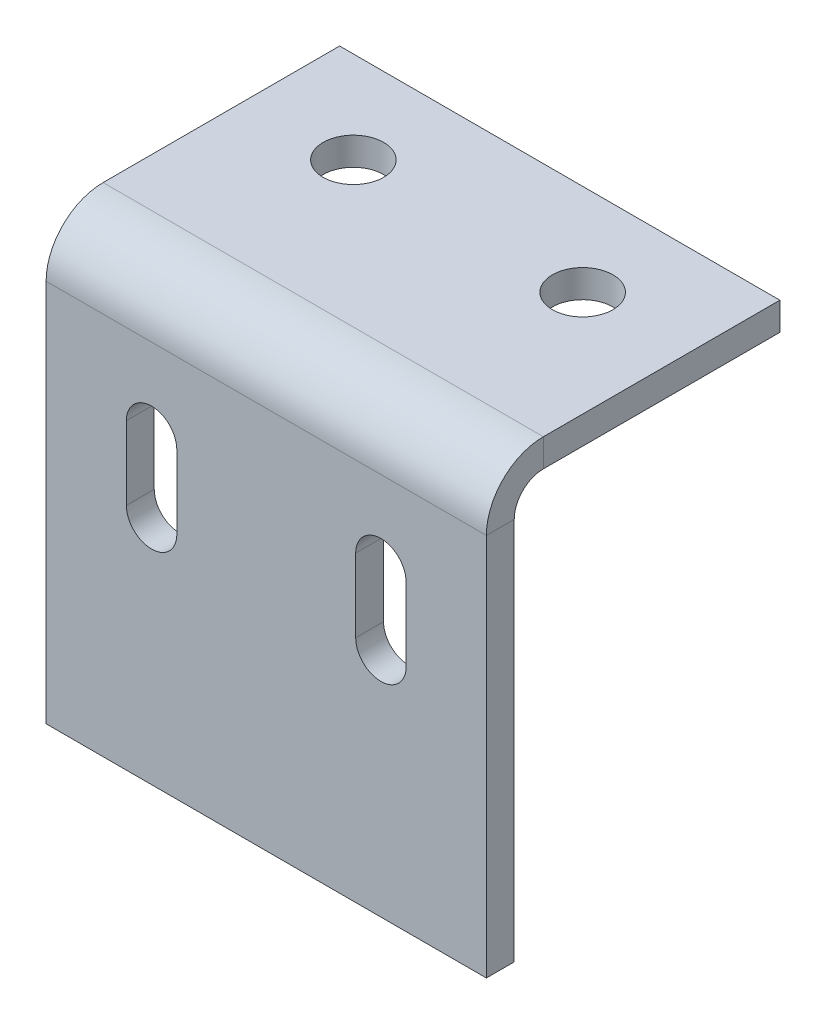
SolidWorks part; units mm, degrees
note: The reader was unsure of these and kept them because the rebuilt part matched: flange length of "Edge-Flange1".
material "Low Carbon Steel"
ref_plane "Front Plane" through (0, 0, 0) normal (0, 0, 1) x (1, 0, 0)
ref_plane "Top Plane" through (0, 0, 0) normal (0, 1, 0) x (1, 0, 0)
ref_plane "Right Plane" through (0, 0, 0) normal (1, 0, 0) x (0, 0, -1)
sketch "Sketch1" plane through (0, 0, 0) normal (0, 1, 0) x (1, 0, 0)
  line L1 (-24, 32) -> (24, 32)
  line L2 (-24, 32) -> (-24, 0)
  line L3 (-24, 0) -> (24, 0)
  line L4 (24, 32) -> (24, 0)
  dimension "D1" = 32
  dimension "D2" = 48
base flange "Base-Flange1" sketch "Sketch1" thickness 3.0378 reverse thickness direction no parameters "D1"=3.175
edge flange "Edge-Flange1" sketch "Sketch8" flange angle 90 flange length 48 flange position material inside bend radius 3.175 thickness 3.0378 relief rectangular parameters "D6"=10
sketch "Sketch8" plane through (0, -3.0378, 0) normal (0, 0, -1) x (1, 0, 0)
  line L1 (24, 0) -> (-24, 0) construction
  line L2 (-24, 0) -> (-24, 44.9622)
  line L3 (-24, 44.9622) -> (24, 44.9622)
  line L4 (24, 44.9622) -> (24, 0)
  line L5 (24, 0) -> (-24, 0)
bend "EdgeBend1" bend radius 3.175 bend angle 90 parameters "D5"=1
hole_wizard "M6 Clearance Hole1" positions "Sketch12" profile "Sketch11" hole size "M6" standard "Peddi DIN" end condition through all
sketch "Sketch12" plane through (0, -3.0378, 0) normal (0, -1, 0) x (-1, 0, 0)
  line L0 (0, 0) -> (0, 22) construction
  line L2 (-12.5, 22) -> (12.5, 22) construction
  line L6 (-24, 0) -> (24, 0) construction
  point P0 (12.5, 22)
  point P2 (-12.5, 22)
  dimension "D1" = 25
  dimension "D2" = 22
sketch "Sketch11" plane through (-12.5, -3.0378, -22) normal (1, 0, 0) x (0, 0, -1)
  line L0 (0, 0) -> (0, 3.0378)
  line L1 (0, 3.0378) -> (3.3, 3.0378)
  line L2 (3.3, 3.0378) -> (3.3, 0)
  line L5 (3.3, 0) -> (0, 0)
  line L11 (0, -6.35) -> (0, 107.95) construction
  dimension "Thru Hole Dia." = 6.6
  dimension "Thru Hole Depth" = 3.0378
sketch "Sketch13" plane through (0, 0, 0) normal (0, 0, 1) x (1, 0, 0)
  line L0 (-12.5, -15) -> (-12.5, -23) construction
  line L1 (-9.75, -15) -> (-9.75, -23)
  line L2 (-15.25, -15) -> (-15.25, -23)
  line L3 (12.5, -15) -> (12.5, -23) construction
  line L4 (15.25, -15) -> (15.25, -23)
  line L5 (9.75, -15) -> (9.75, -23)
  line L6 (15.8, 0) -> (9.2, 0) construction
  line L7 (-12.5, -19) -> (12.5, -19) construction
  line L8 (0, -19) -> (0, 0) construction
  arc A0 (-9.75, -15) -> (-15.25, -15) centre (-12.5, -15) ccw
  arc A1 (-15.25, -23) -> (-9.75, -23) centre (-12.5, -23) ccw
  arc A2 (15.25, -15) -> (9.75, -15) centre (12.5, -15) ccw
  arc A3 (9.75, -23) -> (15.25, -23) centre (12.5, -23) ccw
  point P2 (-12.5, -19)
  point P7 (12.5, -19)
  point P14 (12.5, 0)
  dimension "D1" = 5.5
  dimension "D2" = 8
  dimension "D3" = 19
  dimension "D4" = 25
extrude "Cut-Extrude1" cut sketch "Sketch13" against normal through all normal cut yes
other "Freeze***"
sketch "Bend-Lines1" [suppressed] plane through (0, 0, 0) normal (0, 1, 0) x (1, 0, 0)
sketch "Bounding-Box1" [suppressed] plane through (0, 0, 0) normal (0, 1, 0) x (1, 0, 0)
sheet metal parameters "Sheet-Metal16" thickness 3.0378 parameters "D1"=3.175
flat pattern "Flat-Pattern16" [suppressed]
sketch "Bend-Lines2" plane through (0, 0, 0) normal (0, 1, 0) x (1, 0, 0)
sketch "Bounding-Box2" [suppressed] plane through (0, 0, 0) normal (0, 1, 0) x (1, 0, 0)
sheet metal parameters "Sheet-Metal17" thickness 3.0378 parameters "D1"=3.175
flat pattern "Flat-Pattern16" [suppressed]
sketch "Bend-Lines2" plane through (0, 0, 0) normal (0, 1, 0) x (1, 0, 0)
sketch "Bounding-Box2" [suppressed] plane through (0, 0, 0) normal (0, 1, 0) x (1, 0, 0)
bend of the flat pattern "Flatten-<EdgeBend1>1"
sheet metal parameters "Sheet-Metal19" thickness 3.0378 parameters "D1"=3.175
flat pattern "Flat-Pattern16" [suppressed]
sketch "Bend-Lines2" plane through (0, 0, 0) normal (0, 1, 0) x (1, 0, 0)
sketch "Bounding-Box2" [suppressed] plane through (0, 0, 0) normal (0, 1, 0) x (1, 0, 0)
bend of the flat pattern "Flatten-<EdgeBend1>1"
sheet metal parameters "Sheet-Metal20" thickness 3.0378 parameters "D1"=3.175
flat pattern "Flat-Pattern16"
sketch "Bend-Lines2" plane through (0, 0, 0) normal (0, 1, 0) x (1, 0, 0)
  line L0 (-24, 2.7648) -> (24, 2.7648) construction
  line L1 (-24, 2.7648) -> (24, 2.7648) construction
sketch3d "Bounding-Box2" [suppressed]
  line L0 (-24, 32, 0) -> (-24, -42.4703, 0) construction
  line L1 (24, 32, 0) -> (24, -42.4703, 0) construction
  line L2 (-24, 32, 0) -> (24, 32, 0) construction
  line L3 (-24, -42.4703, 0) -> (24, -42.4703, 0) construction
bend of the flat pattern "Flatten-<EdgeBend1>1"
